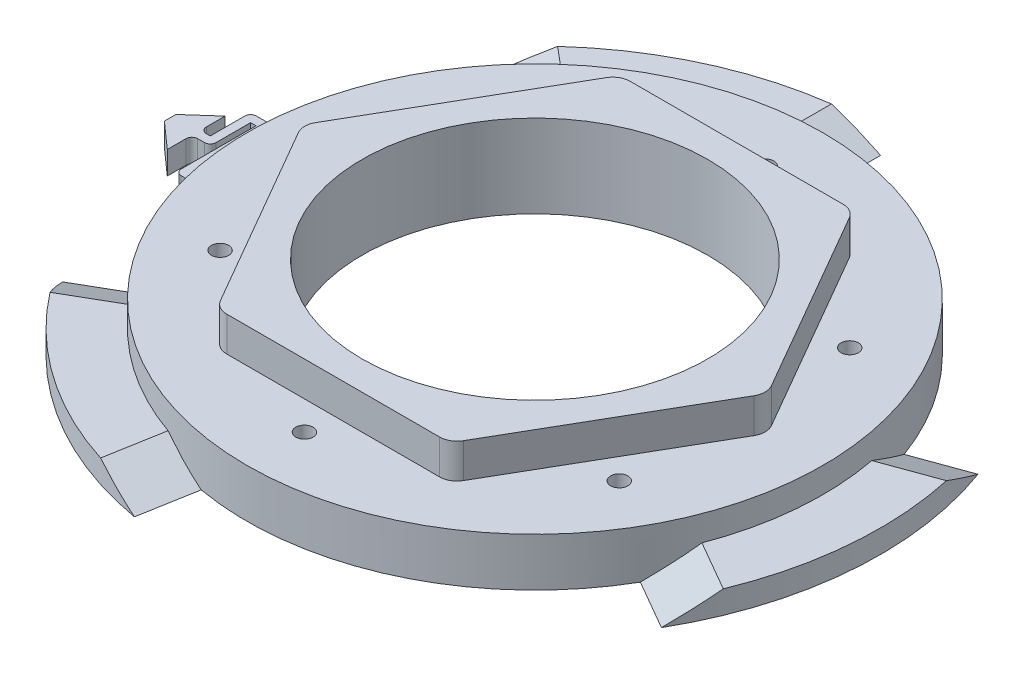
SolidWorks part; units mm, degrees
ref_plane "Ebene vorne" through (0, 0, 0) normal (0, 0, 1) x (1, 0, 0)
ref_plane "Ebene oben" through (0, 0, 0) normal (0, 1, 0) x (1, 0, 0)
ref_plane "Ebene rechts" through (0, 0, 0) normal (1, 0, 0) x (0, 0, -1)
sketch "Skizze1" plane through (0, 0, 0) normal (0, 1, 0) x (1, 0, 0)
  line L0 (0, 0) -> (0, 50) construction
  line L1 (0, 0) -> (-38.3022, 32.1394) construction
  line L2 (-38.3022, 32.1394) -> (-45.9627, 38.5673)
  line L3 (0, 50) -> (0, 60)
  line L4 (46.9846, 17.101) -> (56.3816, 20.5212)
  line L5 (43.3013, -25) -> (51.9615, -30)
  line L6 (-8.6824, -49.2404) -> (-10.4189, -59.0885)
  line L7 (-43.3013, -25) -> (-51.9615, -30)
  arc A0 (-51.9615, -30) -> (-10.4189, -59.0885) centre (0, 0) ccw
  arc A1 (-8.6824, -49.2404) -> (43.3013, -25) centre (0, 0) ccw
  arc A2 (0, 60) -> (-45.9627, 38.5673) centre (0, 0) ccw
  arc A3 (51.9615, -30) -> (56.3816, 20.5212) centre (0, 0) ccw
  arc A4 (46.9846, 17.101) -> (0, 50) centre (0, 0) ccw
  arc A5 (-38.3022, 32.1394) -> (-43.3013, -25) centre (0, 0) ccw
  point P18 (0, 0)
  dimension "D1" = 120
  dimension "D2" = 100
  dimension "D3" = 50
  dimension "D4" = 3
extrude "Aufsatz-Linear austragen1" add sketch "Skizze1" along normal blind 4
sketch "Skizze2" plane through (0, 4, 0) normal (0, 1, 0) x (1, 0, 0)
  circle A0 centre (0, 0) radius 50
extrude "Aufsatz-Linear austragen2" add sketch "Skizze2" along normal blind 4.4
chamfer "Fase1" distance 4 distance2 8 6 edges at (47.6314, 4, 27.5) (51.6831, 4, -18.8111) (0, 4, -55) (-42.1324, 4, -35.3533) (-9.5506, 4, 54.1644) (-47.6314, 4, 27.5) first distance on face at (47.6314, 2, 27.5) first distance on face at (51.6831, 2, -18.8111) first distance on face at (0, 2, -55) first distance on face at (-42.1324, 2, -35.3533) first distance on face at (-9.5506, 2, 54.1644) first distance on face at (-47.6314, 2, 27.5)
sketch "Skizze3" plane through (0, 8.4, 0) normal (0, 1, 0) x (1, 0, 0)
  line L0 (0, 0) -> (40.4145, 0) construction
  line L1 (40.4145, 0) -> (20.2073, 35)
  line L2 (20.2073, 35) -> (-20.2073, 35)
  line L3 (-20.2073, 35) -> (-40.4145, 0)
  line L4 (-40.4145, 0) -> (-20.2073, -35)
  line L5 (-20.2073, -35) -> (20.2073, -35)
  line L6 (20.2073, -35) -> (40.4145, 0)
  circle A0 centre (0, 0) radius 35 construction
  dimension "D1" = 70
extrude "Aufsatz-Linear austragen3" add sketch "Skizze3" along normal blind 6
sketch "Skizze4" plane through (0, 14.4, 0) normal (0, 1, 0) x (1, 0, 0)
  circle A0 centre (0, 0) radius 30
  dimension "D1" = 60
extrude "Schnitt-Linear austragen2" cut sketch "Skizze4" against normal through all
sketch "Skizze5" plane through (0, 0, 0) normal (0, -1, 0) x (1, 0, 0)
  line L0 (-49, 0) -> (-51.4475, 0) construction
  line L1 (-51.4475, 0) -> (-51.4475, 7) construction
  line L2 (-51.4475, 7) -> (-53.895, 7) construction
  line L3 (-53.895, 7) -> (-53.895, -7) construction
  line L4 (-53.895, -7) -> (-56.3425, -7) construction
  line L5 (-56.3425, -7) -> (-56.3425, 0) construction
  line L6 (-56.3425, 0) -> (-61.0453, 0) construction
  line L7 (-51.4475, 0) -> (-56.3425, 0) construction
  line L8 (-58.7878, -5) -> (-63.3028, -5)
  line L9 (-58.7878, -5) -> (-58.7878, -0.75)
  line L10 (-58.7878, 5) -> (-63.3028, 5)
  line L11 (-63.3028, -5) -> (-63.3028, 5)
  line L12 (-58.7878, -5) -> (-63.3028, 5) construction
  line L13 (-58.7878, 5) -> (-63.3028, -5) construction
  line L14 (-48.9943, 0.75) -> (-50.6975, 0.75)
  line L15 (-50.6975, 0.75) -> (-50.6975, 7.75)
  line L16 (-50.6975, 7.75) -> (-54.645, 7.75)
  line L17 (-54.645, 7.75) -> (-54.645, -6.25)
  line L18 (-54.645, -6.25) -> (-55.5925, -6.25)
  line L19 (-55.5925, -6.25) -> (-55.5925, 0.75)
  line L20 (-55.5925, 0.75) -> (-58.7878, 0.75)
  line L21 (-48.9943, -0.75) -> (-52.1975, -0.75)
  line L22 (-52.1975, -0.75) -> (-52.1975, 6.25)
  line L23 (-52.1975, 6.25) -> (-53.145, 6.25)
  line L24 (-53.145, 6.25) -> (-53.145, -7.75)
  line L25 (-53.145, -7.75) -> (-57.0925, -7.75)
  line L26 (-57.0925, -7.75) -> (-57.0925, -0.75)
  line L27 (-57.0925, -0.75) -> (-58.7878, -0.75)
  line L28 (-58.7878, 0.75) -> (-58.7878, 5)
  line L29 (-49, -0.75) -> (-52.1975, -0.75) construction
  line L30 (-57.0925, -0.75) -> (-61.0453, -0.75) construction
  line L31 (-55.5925, 0.75) -> (-61.0453, 0.75) construction
  line L32 (-49, 0.75) -> (-50.6975, 0.75) construction
  arc A0 (-48.9943, 0.75) -> (-48.9943, -0.75) centre (0, 0) ccw
  circle A1 centre (0, 0) radius 63.5 construction
  circle A2 centre (0, 0) radius 59 construction
  dimension "D1" = 98
  dimension "D2" = 127
  dimension "D3" = 118
  dimension "D4" = 10
  dimension "D5" = 2.4475
  dimension "D6" = 2.4475
  dimension "D7" = 2.4475
  dimension "D8" = 7
  dimension "D9" = 14
  dimension "D10" = 0.75
  dimension "D11" = 0.75
extrude "Aufsatz-Linear austragen4" add sketch "Skizze5" against normal up to surface (4 mm away) up to face at (-30.8851, 4, 44.1086)
fillet "Verrundung2" radius 1 10 edges at (-49.9944, 2, 0.75) (-49.9944, 2, -0.75) (-58.7878, 2, -0.75) (-58.7878, 2, 0.75) (-55.5925, 2, 0.75) (-50.6975, 2, 7.75) (-54.645, 2, 7.75) (-57.0925, 2, -7.75) (-53.145, 2, -7.75) (-52.1975, 2, -0.75)
chamfer "Fase2" distance 4 distance2 4.5 1 edges at (-63.3028, 2, 5) first distance on face at (-63.3028, 2, 0)
chamfer "Fase3" distance 4.5 distance2 4 1 edges at (-63.3028, 2, -5) first distance on face at (-61.0453, 2, -5)
fillet "Verrundung3" radius 3 6 edges at (-20.2073, 11.4, 35) (20.2073, 11.4, 35) (40.4145, 11.4, 0) (-40.4145, 11.4, 0) (-20.2073, 11.4, -35) (20.2073, 11.4, -35)
sketch "Skizze6" plane through (0, 8.4, 0) normal (0, 1, 0) x (1, 0, 0)
  line L0 (0, 0) -> (0, 40) construction
  circle A0 centre (0, 40) radius 1.5
  circle A1 centre (34.641, 20) radius 1.5
  circle A2 centre (34.641, -20) radius 1.5
  circle A3 centre (0, -40) radius 1.5
  circle A4 centre (-34.641, -20) radius 1.5
  circle A5 centre (-34.641, 20) radius 1.5
  point P16 (0, 0)
  dimension "D1" = 3
  dimension "D2" = 40
  dimension "D3" = 6
extrude "Schnitt-Linear austragen3" cut sketch "Skizze6" against normal through all
